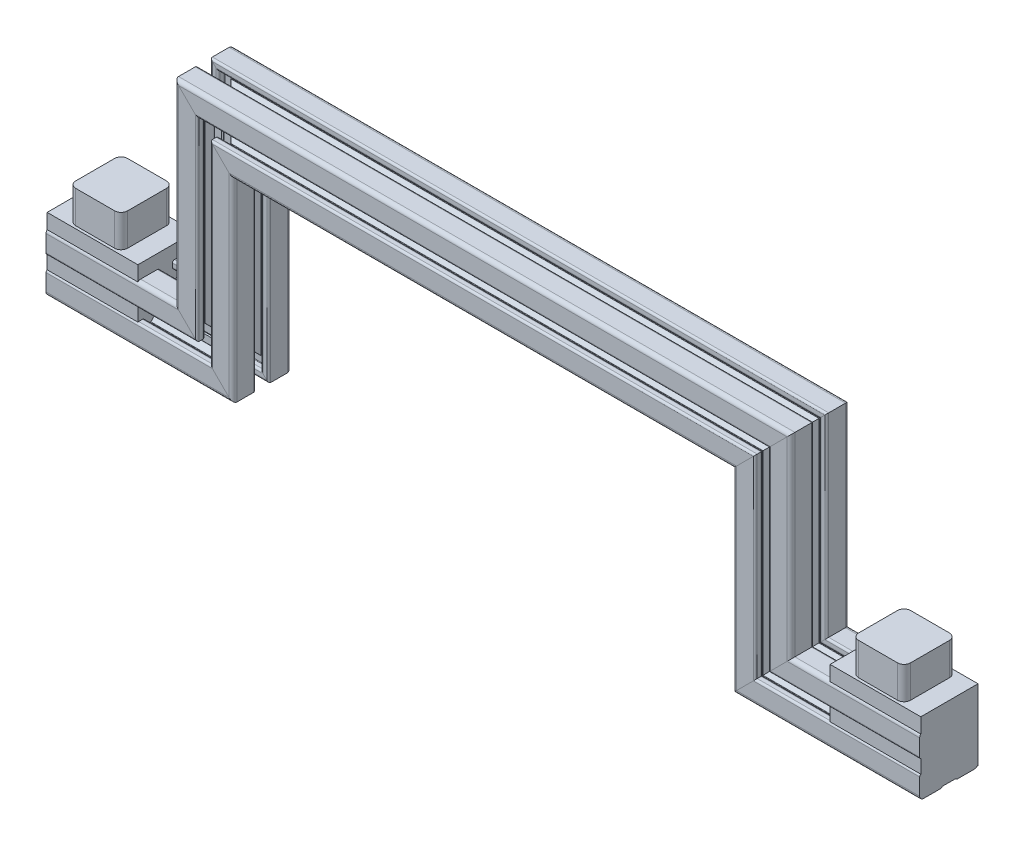
SolidWorks part; units mm, degrees
material "Commercially Pure CP-Ti UNS R50400 (SS)"
ref_plane "Front Plane" through (0, 0, 0) normal (0, 0, 1) x (1, 0, 0)
ref_plane "Top Plane" through (0, 0, 0) normal (0, 1, 0) x (1, 0, 0)
ref_plane "Right Plane" through (0, 0, 0) normal (1, 0, 0) x (0, 0, -1)
sketch "Sketch7" plane through (0, 0, 0) normal (1, 0, 0) x (0, 0, -1)
  line L0 (13.9698, 21.2743) -> (13.5298, 21.2743)
  line L1 (12.0298, 22.7743) -> (12.0298, 23.2743)
  line L2 (13.5298, 24.7743) -> (23.1398, 24.7743)
  line L3 (25.4198, 22.4943) -> (25.4198, 12.8843)
  line L4 (23.9198, 11.3843) -> (23.4198, 11.3843)
  line L5 (21.9198, 12.8843) -> (21.9198, 13.3243)
  line L6 (20.9198, 14.3243) -> (15.3498, 14.3243)
  line L7 (14.9698, 14.7043) -> (14.9698, 20.2743)
  line L8 (21.9589, -6.6897) -> (21.9589, -6.2497)
  line L9 (23.4589, -4.7497) -> (23.9589, -4.7497)
  line L10 (25.4589, -6.2497) -> (25.4589, -15.8597)
  line L11 (23.1789, -18.1397) -> (13.5689, -18.1397)
  line L12 (12.0689, -16.6397) -> (12.0689, -16.1397)
  line L13 (13.5689, -14.6397) -> (14.0089, -14.6397)
  line L14 (15.0089, -13.6397) -> (15.0089, -8.0697)
  line L15 (15.3889, -7.6897) -> (20.9589, -7.6897)
  line L16 (-6.0052, -14.6787) -> (-5.5652, -14.6787)
  line L17 (-4.0652, -16.1787) -> (-4.0652, -16.6787)
  line L18 (-5.5652, -18.1787) -> (-15.1752, -18.1787)
  line L19 (-17.4552, -15.8987) -> (-17.4552, -6.2887)
  line L20 (-15.9552, -4.7887) -> (-15.4552, -4.7887)
  line L21 (-13.9552, -6.2887) -> (-13.9552, -6.7287)
  line L22 (-12.9552, -7.7287) -> (-7.3852, -7.7287)
  line L23 (-7.0052, -8.1087) -> (-7.0052, -13.6787)
  line L24 (1.8289, -2.4886) -> (1.4132, -2.3164)
  line L25 (-1.632, 0.7289) -> (-1.8042, 1.1447)
  line L26 (-1.804, 5.4512) -> (-1.6318, 5.867)
  line L27 (1.4134, 8.9121) -> (1.8292, 9.0843)
  line L28 (6.1358, 9.0842) -> (6.5515, 8.912)
  line L29 (9.5966, 5.8667) -> (9.7688, 5.451)
  line L30 (9.7687, 1.1444) -> (9.5965, 0.7287)
  line L31 (6.5512, -2.3165) -> (6.1355, -2.4887)
  line L32 (-13.9942, 13.2853) -> (-13.9942, 12.8453)
  line L33 (-15.4942, 11.3453) -> (-15.9942, 11.3453)
  line L34 (-17.4942, 12.8453) -> (-17.4942, 22.4553)
  line L35 (-15.2142, 24.7353) -> (-5.6042, 24.7353)
  line L36 (-4.1042, 23.2353) -> (-4.1042, 22.7353)
  line L37 (-5.6042, 21.2353) -> (-6.0442, 21.2353)
  line L38 (-7.0442, 20.2353) -> (-7.0442, 14.6653)
  line L39 (-7.4242, 14.2853) -> (-12.9942, 14.2853)
  line L40 (4.9058, 11.2153) -> (4.0058, 10.7002)
  line L41 (4.0058, 10.7002) -> (3.1058, 11.2153)
  line L42 (3.1058, 11.2153) -> (-2.1975, 11.2153)
  line L43 (-2.4662, 11.3266) -> (-5.9329, 14.7933)
  line L44 (-6.0442, 15.062) -> (-6.0442, 19.3553)
  line L45 (-5.6642, 19.7353) -> (-2.5792, 19.7353)
  line L46 (-1.0592, 21.2553) -> (-1.0592, 24.2153)
  line L47 (-2.5792, 25.7353) -> (-15.4942, 25.7353)
  line L48 (-18.4942, 22.7353) -> (-18.4942, 9.8203)
  line L49 (-16.9742, 8.3003) -> (-14.0142, 8.3003)
  line L50 (-12.4942, 9.8203) -> (-12.4942, 12.9053)
  line L51 (-12.1142, 13.2853) -> (-7.8138, 13.2853)
  line L52 (-7.5451, 13.174) -> (-4.0855, 9.7144)
  line L53 (-3.9742, 9.4457) -> (-3.9742, 4.1353)
  line L54 (-3.9742, 4.1353) -> (-3.4546, 3.2353)
  line L55 (-3.4546, 3.2353) -> (-3.9742, 2.3353)
  line L56 (-3.9742, 2.3353) -> (-3.9742, -2.968)
  line L57 (-4.0855, -3.2367) -> (-7.5522, -6.7034)
  line L58 (-7.8209, -6.8147) -> (-12.1142, -6.8147)
  line L59 (-12.4942, -6.4347) -> (-12.4942, -3.3497)
  line L60 (-14.0142, -1.8297) -> (-16.9742, -1.8297)
  line L61 (-18.4942, -3.3497) -> (-18.4942, -16.2647)
  line L62 (-15.4942, -19.2647) -> (-2.5792, -19.2647)
  line L63 (-1.0592, -17.7447) -> (-1.0592, -14.7847)
  line L64 (-2.5792, -13.2647) -> (-5.6642, -13.2647)
  line L65 (-6.0442, -12.8847) -> (-6.0442, -8.5843)
  line L66 (-5.9329, -8.3156) -> (-2.4733, -4.856)
  line L67 (-2.2046, -4.7447) -> (3.1058, -4.7447)
  line L68 (3.1058, -4.7447) -> (4.0058, -4.2295)
  line L69 (4.0058, -4.2295) -> (4.9058, -4.7447)
  line L70 (4.9058, -4.7447) -> (10.2091, -4.7447)
  line L71 (10.4778, -4.856) -> (13.9445, -8.3227)
  line L72 (14.0558, -8.5914) -> (14.0558, -12.8847)
  line L73 (13.6758, -13.2647) -> (10.5908, -13.2647)
  line L74 (9.0708, -14.7847) -> (9.0708, -17.7447)
  line L75 (10.5908, -19.2647) -> (23.5058, -19.2647)
  line L76 (26.5058, -16.2647) -> (26.5058, -3.3497)
  line L77 (24.9858, -1.8297) -> (22.0258, -1.8297)
  line L78 (20.5058, -3.3497) -> (20.5058, -6.4347)
  line L79 (20.1258, -6.8147) -> (15.8254, -6.8147)
  line L80 (15.5567, -6.7034) -> (12.0971, -3.2438)
  line L81 (11.9858, -2.9751) -> (11.9858, 2.3353)
  line L82 (11.9858, 2.3353) -> (11.4662, 3.2353)
  line L83 (11.4662, 3.2353) -> (11.9858, 4.1353)
  line L84 (11.9858, 4.1353) -> (11.9858, 9.4386)
  line L85 (12.0971, 9.7073) -> (15.5638, 13.174)
  line L86 (15.8325, 13.2853) -> (20.1258, 13.2853)
  line L87 (20.5058, 12.9053) -> (20.5058, 9.8203)
  line L88 (22.0258, 8.3003) -> (24.9858, 8.3003)
  line L89 (26.5058, 9.8203) -> (26.5058, 22.7353)
  line L90 (23.5058, 25.7353) -> (10.5908, 25.7353)
  line L91 (9.0708, 24.2153) -> (9.0708, 21.2553)
  line L92 (10.5908, 19.7353) -> (13.6758, 19.7353)
  line L93 (14.0558, 19.3553) -> (14.0558, 15.0549)
  line L94 (13.9445, 14.7862) -> (10.4849, 11.3266)
  line L95 (10.2162, 11.2153) -> (4.9058, 11.2153)
  arc A0 (14.9698, 20.2743) -> (13.9698, 21.2743) centre (13.9698, 20.2743) ccw
  arc A1 (12.0298, 22.7743) -> (13.5298, 21.2743) centre (13.5298, 22.7743) ccw
  arc A2 (13.5298, 24.7743) -> (12.0298, 23.2743) centre (13.5298, 23.2743) ccw
  arc A3 (25.4198, 22.4943) -> (23.1398, 24.7743) centre (23.1398, 22.4943) ccw
  arc A4 (23.9198, 11.3843) -> (25.4198, 12.8843) centre (23.9198, 12.8843) ccw
  arc A5 (21.9198, 12.8843) -> (23.4198, 11.3843) centre (23.4198, 12.8843) ccw
  arc A6 (21.9198, 13.3243) -> (20.9198, 14.3243) centre (20.9198, 13.3243) ccw
  arc A7 (14.9698, 14.7043) -> (15.3498, 14.3243) centre (15.3498, 14.7043) ccw
  arc A8 (20.9589, -7.6897) -> (21.9589, -6.6897) centre (20.9589, -6.6897) ccw
  arc A9 (23.4589, -4.7497) -> (21.9589, -6.2497) centre (23.4589, -6.2497) ccw
  arc A10 (25.4589, -6.2497) -> (23.9589, -4.7497) centre (23.9589, -6.2497) ccw
  arc A11 (23.1789, -18.1397) -> (25.4589, -15.8597) centre (23.1789, -15.8597) ccw
  arc A12 (12.0689, -16.6397) -> (13.5689, -18.1397) centre (13.5689, -16.6397) ccw
  arc A13 (13.5689, -14.6397) -> (12.0689, -16.1397) centre (13.5689, -16.1397) ccw
  arc A14 (14.0089, -14.6397) -> (15.0089, -13.6397) centre (14.0089, -13.6397) ccw
  arc A15 (15.3889, -7.6897) -> (15.0089, -8.0697) centre (15.3889, -8.0697) ccw
  arc A16 (-7.0052, -13.6787) -> (-6.0052, -14.6787) centre (-6.0052, -13.6787) ccw
  arc A17 (-4.0652, -16.1787) -> (-5.5652, -14.6787) centre (-5.5652, -16.1787) ccw
  arc A18 (-5.5652, -18.1787) -> (-4.0652, -16.6787) centre (-5.5652, -16.6787) ccw
  arc A19 (-17.4552, -15.8987) -> (-15.1752, -18.1787) centre (-15.1752, -15.8987) ccw
  arc A20 (-15.9552, -4.7887) -> (-17.4552, -6.2887) centre (-15.9552, -6.2887) ccw
  arc A21 (-13.9552, -6.2887) -> (-15.4552, -4.7887) centre (-15.4552, -6.2887) ccw
  arc A22 (-13.9552, -6.7287) -> (-12.9552, -7.7287) centre (-12.9552, -6.7287) ccw
  arc A23 (-7.0052, -8.1087) -> (-7.3852, -7.7287) centre (-7.3852, -8.1087) ccw
  arc A24 (1.0363, -0.7421) -> (1.4132, -2.3164) centre (1.7959, -1.3925) ccw
  arc A25 (-0.0577, 0.352) -> (1.0363, -0.7421) centre (3.9823, 3.2978) ccw
  arc A26 (-1.632, 0.7289) -> (-0.0577, 0.352) centre (-0.7081, 1.1116) ccw
  arc A27 (-0.9575, 2.5244) -> (-1.8042, 1.1447) centre (-0.8803, 1.5274) ccw
  arc A28 (-0.9574, 4.0715) -> (-0.9575, 2.5244) centre (3.9823, 3.2978) ccw
  arc A29 (-1.804, 5.4512) -> (-0.9574, 4.0715) centre (-0.8802, 5.0686) ccw
  arc A30 (-0.0575, 6.2439) -> (-1.6318, 5.867) centre (-0.708, 5.4843) ccw
  arc A31 (1.0365, 7.3379) -> (-0.0575, 6.2439) centre (3.9823, 3.2978) ccw
  arc A32 (1.4134, 8.9121) -> (1.0365, 7.3379) centre (1.7961, 7.9882) ccw
  arc A33 (3.2089, 8.2376) -> (1.8292, 9.0843) centre (2.2119, 8.1604) ccw
  arc A34 (4.7561, 8.2376) -> (3.2089, 8.2376) centre (3.9823, 3.2978) ccw
  arc A35 (6.1358, 9.0842) -> (4.7561, 8.2376) centre (5.7531, 8.1603) ccw
  arc A36 (6.9284, 7.3377) -> (6.5515, 8.912) centre (6.1688, 7.9881) ccw
  arc A37 (8.0224, 6.2437) -> (6.9284, 7.3377) centre (3.9823, 3.2978) ccw
  arc A38 (9.5966, 5.8667) -> (8.0224, 6.2437) centre (8.6727, 5.484) ccw
  arc A39 (8.9222, 4.0713) -> (9.7688, 5.451) centre (8.845, 5.0683) ccw
  arc A40 (8.9221, 2.5241) -> (8.9222, 4.0713) centre (3.9823, 3.2978) ccw
  arc A41 (9.7687, 1.1444) -> (8.9221, 2.5241) centre (8.8448, 1.5271) ccw
  arc A42 (8.0222, 0.3518) -> (9.5965, 0.7287) centre (8.6726, 1.1113) ccw
  arc A43 (6.9282, -0.7422) -> (8.0222, 0.3518) centre (3.9823, 3.2978) ccw
  arc A44 (6.5512, -2.3165) -> (6.9282, -0.7422) centre (6.1685, -1.3926) ccw
  arc A45 (4.7558, -1.642) -> (6.1355, -2.4887) centre (5.7528, -1.5648) ccw
  arc A46 (3.2086, -1.642) -> (4.7558, -1.642) centre (3.9823, 3.2978) ccw
  arc A47 (1.8289, -2.4886) -> (3.2086, -1.642) centre (2.2116, -1.5647) ccw
  arc A48 (-12.9942, 14.2853) -> (-13.9942, 13.2853) centre (-12.9942, 13.2853) ccw
  arc A49 (-15.4942, 11.3453) -> (-13.9942, 12.8453) centre (-15.4942, 12.8453) ccw
  arc A50 (-17.4942, 12.8453) -> (-15.9942, 11.3453) centre (-15.9942, 12.8453) ccw
  arc A51 (-15.2142, 24.7353) -> (-17.4942, 22.4553) centre (-15.2142, 22.4553) ccw
  arc A52 (-4.1042, 23.2353) -> (-5.6042, 24.7353) centre (-5.6042, 23.2353) ccw
  arc A53 (-5.6042, 21.2353) -> (-4.1042, 22.7353) centre (-5.6042, 22.7353) ccw
  arc A54 (-6.0442, 21.2353) -> (-7.0442, 20.2353) centre (-6.0442, 20.2353) ccw
  arc A55 (-7.4242, 14.2853) -> (-7.0442, 14.6653) centre (-7.4242, 14.6653) ccw
  arc A56 (-2.4662, 11.3266) -> (-2.1975, 11.2153) centre (-2.1975, 11.5953) ccw
  arc A57 (-6.0442, 15.062) -> (-5.9329, 14.7933) centre (-5.6642, 15.062) ccw
  arc A58 (-5.6642, 19.7353) -> (-6.0442, 19.3553) centre (-5.6642, 19.3553) ccw
  arc A59 (-2.5792, 19.7353) -> (-1.0592, 21.2553) centre (-2.5792, 21.2553) ccw
  arc A60 (-1.0592, 24.2153) -> (-2.5792, 25.7353) centre (-2.5792, 24.2153) ccw
  arc A61 (-15.4942, 25.7353) -> (-18.4942, 22.7353) centre (-15.4942, 22.7353) ccw
  arc A62 (-18.4942, 9.8203) -> (-16.9742, 8.3003) centre (-16.9742, 9.8203) ccw
  arc A63 (-14.0142, 8.3003) -> (-12.4942, 9.8203) centre (-14.0142, 9.8203) ccw
  arc A64 (-12.1142, 13.2853) -> (-12.4942, 12.9053) centre (-12.1142, 12.9053) ccw
  arc A65 (-7.5451, 13.174) -> (-7.8138, 13.2853) centre (-7.8138, 12.9053) ccw
  arc A66 (-3.9742, 9.4457) -> (-4.0855, 9.7144) centre (-4.3542, 9.4457) ccw
  arc A67 (-4.0855, -3.2367) -> (-3.9742, -2.968) centre (-4.3542, -2.968) ccw
  arc A68 (-7.8209, -6.8147) -> (-7.5522, -6.7034) centre (-7.8209, -6.4347) ccw
  arc A69 (-12.4942, -6.4347) -> (-12.1142, -6.8147) centre (-12.1142, -6.4347) ccw
  arc A70 (-12.4942, -3.3497) -> (-14.0142, -1.8297) centre (-14.0142, -3.3497) ccw
  arc A71 (-16.9742, -1.8297) -> (-18.4942, -3.3497) centre (-16.9742, -3.3497) ccw
  arc A72 (-18.4942, -16.2647) -> (-15.4942, -19.2647) centre (-15.4942, -16.2647) ccw
  arc A73 (-2.5792, -19.2647) -> (-1.0592, -17.7447) centre (-2.5792, -17.7447) ccw
  arc A74 (-1.0592, -14.7847) -> (-2.5792, -13.2647) centre (-2.5792, -14.7847) ccw
  arc A75 (-6.0442, -12.8847) -> (-5.6642, -13.2647) centre (-5.6642, -12.8847) ccw
  arc A76 (-5.9329, -8.3156) -> (-6.0442, -8.5843) centre (-5.6642, -8.5843) ccw
  arc A77 (-2.2046, -4.7447) -> (-2.4733, -4.856) centre (-2.2046, -5.1247) ccw
  arc A78 (10.4778, -4.856) -> (10.2091, -4.7447) centre (10.2091, -5.1247) ccw
  arc A79 (14.0558, -8.5914) -> (13.9445, -8.3227) centre (13.6758, -8.5914) ccw
  arc A80 (13.6758, -13.2647) -> (14.0558, -12.8847) centre (13.6758, -12.8847) ccw
  arc A81 (10.5908, -13.2647) -> (9.0708, -14.7847) centre (10.5908, -14.7847) ccw
  arc A82 (9.0708, -17.7447) -> (10.5908, -19.2647) centre (10.5908, -17.7447) ccw
  arc A83 (23.5058, -19.2647) -> (26.5058, -16.2647) centre (23.5058, -16.2647) ccw
  arc A84 (26.5058, -3.3497) -> (24.9858, -1.8297) centre (24.9858, -3.3497) ccw
  arc A85 (22.0258, -1.8297) -> (20.5058, -3.3497) centre (22.0258, -3.3497) ccw
  arc A86 (20.1258, -6.8147) -> (20.5058, -6.4347) centre (20.1258, -6.4347) ccw
  arc A87 (15.5567, -6.7034) -> (15.8254, -6.8147) centre (15.8254, -6.4347) ccw
  arc A88 (11.9858, -2.9751) -> (12.0971, -3.2438) centre (12.3658, -2.9751) ccw
  arc A89 (12.0971, 9.7073) -> (11.9858, 9.4386) centre (12.3658, 9.4386) ccw
  arc A90 (15.8325, 13.2853) -> (15.5638, 13.174) centre (15.8325, 12.9053) ccw
  arc A91 (20.5058, 12.9053) -> (20.1258, 13.2853) centre (20.1258, 12.9053) ccw
  arc A92 (20.5058, 9.8203) -> (22.0258, 8.3003) centre (22.0258, 9.8203) ccw
  arc A93 (24.9858, 8.3003) -> (26.5058, 9.8203) centre (24.9858, 9.8203) ccw
  arc A94 (26.5058, 22.7353) -> (23.5058, 25.7353) centre (23.5058, 22.7353) ccw
  arc A95 (10.5908, 25.7353) -> (9.0708, 24.2153) centre (10.5908, 24.2153) ccw
  arc A96 (9.0708, 21.2553) -> (10.5908, 19.7353) centre (10.5908, 21.2553) ccw
  arc A97 (14.0558, 19.3553) -> (13.6758, 19.7353) centre (13.6758, 19.3553) ccw
  arc A98 (13.9445, 14.7862) -> (14.0558, 15.0549) centre (13.6758, 15.0549) ccw
  arc A99 (10.2162, 11.2153) -> (10.4849, 11.3266) centre (10.2162, 11.5953) ccw
sketch "Sketch1" plane through (0, 0, 0) normal (0, 0, 1) x (1, 0, 0)
  line L0 (0, 0) -> (125, 0)
  line L1 (125, 0) -> (125, 150)
  line L2 (125, 150) -> (337, 150)
  dimension "D1" = 337
  dimension "D2" = 125
  dimension "D3" = 150
sketch "Sketch2" [suppressed] plane through (0, 0, 0) normal (1, 0, 0) x (0, 0, -1)
  line L0 (-33.5, -41) -> (-31.5, -41)
  line L1 (-31.5, -43) -> (-42, -43)
  line L2 (-43, -42) -> (-43, -31.5)
  line L3 (-41, -31.5) -> (-41, -33.5)
  line L4 (-40, -34.5) -> (-34.88, -34.5)
  line L5 (-34.5, -34.88) -> (-34.5, -40)
  line L6 (-16.657, -26.2238) -> (-18.284, -25.188)
  line L7 (-19.8123, -26.7162) -> (-18.7764, -28.3429)
  line L8 (-21.0015, -29.2647) -> (-21.4195, -27.3819)
  line L9 (-23.5808, -27.3818) -> (-23.9986, -29.2645)
  line L10 (-26.2238, -28.343) -> (-25.188, -26.716)
  line L11 (-26.7162, -25.1877) -> (-28.3429, -26.2236)
  line L12 (-29.2647, -23.9985) -> (-27.3819, -23.5805)
  line L13 (-27.3818, -21.4192) -> (-29.2645, -21.0014)
  line L14 (-28.343, -18.7762) -> (-26.716, -19.812)
  line L15 (-25.1877, -18.2838) -> (-26.2236, -16.6571)
  line L16 (-23.9985, -15.7353) -> (-23.5805, -17.6181)
  line L17 (-21.4192, -17.6182) -> (-21.0014, -15.7355)
  line L18 (-18.7762, -16.657) -> (-19.812, -18.284)
  line L19 (-18.2838, -19.8123) -> (-16.6571, -18.7764)
  line L20 (-15.7353, -21.0015) -> (-17.6181, -21.4195)
  line L21 (-17.6182, -23.5808) -> (-15.7355, -23.9986)
  line L22 (41, -33.5) -> (41, -31.5)
  line L23 (43, -31.5) -> (43, -42)
  line L24 (42, -43) -> (31.5, -43)
  line L25 (31.5, -41) -> (33.5, -41)
  line L26 (34.5, -40) -> (34.5, -34.88)
  line L27 (34.88, -34.5) -> (40, -34.5)
  line L28 (26.7162, -19.8123) -> (28.3429, -18.7764)
  line L29 (29.2647, -21.0015) -> (27.3819, -21.4195)
  line L30 (27.3818, -23.5808) -> (29.2645, -23.9986)
  line L31 (28.343, -26.2238) -> (26.716, -25.188)
  line L32 (25.1877, -26.7162) -> (26.2236, -28.3429)
  line L33 (23.9985, -29.2647) -> (23.5805, -27.3819)
  line L34 (21.4192, -27.3818) -> (21.0014, -29.2645)
  line L35 (18.7762, -28.343) -> (19.812, -26.716)
  line L36 (18.2838, -25.1877) -> (16.6571, -26.2236)
  line L37 (15.7353, -23.9985) -> (17.6181, -23.5805)
  line L38 (17.6182, -21.4192) -> (15.7355, -21.0014)
  line L39 (16.657, -18.7762) -> (18.284, -19.812)
  line L40 (19.8123, -18.2838) -> (18.7764, -16.6571)
  line L41 (21.0015, -15.7353) -> (21.4195, -17.6181)
  line L42 (23.5808, -17.6182) -> (23.9986, -15.7355)
  line L43 (26.2238, -16.657) -> (25.188, -18.284)
  line L44 (34.5, 34.88) -> (34.5, 40)
  line L45 (33.5, 41) -> (31.5, 41)
  line L46 (31.5, 43) -> (42, 43)
  line L47 (43, 42) -> (43, 31.5)
  line L48 (41, 31.5) -> (41, 33.5)
  line L49 (40, 34.5) -> (34.88, 34.5)
  line L50 (26.7162, 25.1877) -> (28.3429, 26.2236)
  line L51 (29.2647, 23.9985) -> (27.3819, 23.5805)
  line L52 (27.3818, 21.4192) -> (29.2645, 21.0014)
  line L53 (28.343, 18.7762) -> (26.716, 19.812)
  line L54 (25.1877, 18.2838) -> (26.2236, 16.6571)
  line L55 (23.9985, 15.7353) -> (23.5805, 17.6181)
  line L56 (21.4192, 17.6182) -> (21.0014, 15.7355)
  line L57 (18.7762, 16.657) -> (19.812, 18.284)
  line L58 (18.2838, 19.8123) -> (16.6571, 18.7764)
  line L59 (15.7353, 21.0015) -> (17.6181, 21.4195)
  line L60 (17.6182, 23.5808) -> (15.7355, 23.9986)
  line L61 (16.657, 26.2238) -> (18.284, 25.188)
  line L62 (19.8123, 26.7162) -> (18.7764, 28.3429)
  line L63 (21.0015, 29.2647) -> (21.4195, 27.3819)
  line L64 (23.5808, 27.3818) -> (23.9986, 29.2645)
  line L65 (26.2238, 28.343) -> (25.188, 26.716)
  line L66 (-41, 33.5) -> (-41, 31.5)
  line L67 (-43, 31.5) -> (-43, 42)
  line L68 (-42, 43) -> (-31.5, 43)
  line L69 (-31.5, 41) -> (-33.5, 41)
  line L70 (-34.5, 40) -> (-34.5, 34.88)
  line L71 (-34.88, 34.5) -> (-40, 34.5)
  line L72 (-16.657, 18.7762) -> (-18.284, 19.812)
  line L73 (-19.8123, 18.2838) -> (-18.7764, 16.6571)
  line L74 (-21.0015, 15.7353) -> (-21.4195, 17.6181)
  line L75 (-23.5808, 17.6182) -> (-23.9986, 15.7355)
  line L76 (-26.2238, 16.657) -> (-25.188, 18.284)
  line L77 (-26.7162, 19.8123) -> (-28.3429, 18.7764)
  line L78 (-29.2647, 21.0015) -> (-27.3819, 21.4195)
  line L79 (-27.3818, 23.5808) -> (-29.2645, 23.9986)
  line L80 (-28.343, 26.2238) -> (-26.716, 25.188)
  line L81 (-25.1877, 26.7162) -> (-26.2236, 28.3429)
  line L82 (-23.9985, 29.2647) -> (-23.5805, 27.3819)
  line L83 (-21.4192, 27.3818) -> (-21.0014, 29.2645)
  line L84 (-18.7762, 28.343) -> (-19.812, 26.716)
  line L85 (-18.2838, 25.1877) -> (-16.6571, 26.2236)
  line L86 (-15.7353, 23.9985) -> (-17.6181, 23.5805)
  line L87 (-17.6182, 21.4192) -> (-15.7355, 21.0014)
  line L88 (39, -10.16) -> (33.3774, -10.16)
  line L89 (31.9632, -10.7458) -> (29.8203, -12.8887)
  line L90 (29.5516, -13) -> (23.4, -13)
  line L91 (23.4, -13) -> (22.5, -13.5151)
  line L92 (22.5, -13.5151) -> (21.6, -13)
  line L93 (21.6, -13) -> (15, -13)
  line L94 (13, -15) -> (13, -21.6)
  line L95 (13, -21.6) -> (13.5196, -22.5)
  line L96 (13.5196, -22.5) -> (13, -23.4)
  line L97 (13, -23.4) -> (13, -29.5516)
  line L98 (12.8887, -29.8203) -> (11.3787, -31.3303)
  line L99 (10.5, -33.4516) -> (10.5, -40)
  line L100 (11.5, -41) -> (13.5, -41)
  line L101 (13.5, -43) -> (-13.5, -43)
  line L102 (-13.5, -41) -> (-11.5, -41)
  line L103 (-10.5, -40) -> (-10.5, -33.4516)
  line L104 (-11.3787, -31.3303) -> (-12.8887, -29.8203)
  line L105 (-13, -29.5516) -> (-13, -23.4)
  line L106 (-13, -23.4) -> (-13.5196, -22.5)
  line L107 (-13.5196, -22.5) -> (-13, -21.6)
  line L108 (-13, -21.6) -> (-13, -15)
  line L109 (-15, -13) -> (-21.6, -13)
  line L110 (-21.6, -13) -> (-22.5, -13.5151)
  line L111 (-22.5, -13.5151) -> (-23.4, -13)
  line L112 (-23.4, -13) -> (-29.5516, -13)
  line L113 (-29.8203, -12.8887) -> (-31.9632, -10.7458)
  line L114 (-33.3774, -10.16) -> (-39, -10.16)
  line L115 (-41, -12.16) -> (-41, -13.5)
  line L116 (-43, -13.5) -> (-43, 13.5)
  line L117 (-41, 13.5) -> (-41, 12.16)
  line L118 (-39, 10.16) -> (-33.3774, 10.16)
  line L119 (-31.9632, 10.7458) -> (-29.8203, 12.8887)
  line L120 (-29.5516, 13) -> (-23.4, 13)
  line L121 (-23.4, 13) -> (-22.5, 13.5151)
  line L122 (-22.5, 13.5151) -> (-21.6, 13)
  line L123 (-21.6, 13) -> (-15, 13)
  line L124 (-13, 15) -> (-13, 21.6)
  line L125 (-13, 21.6) -> (-13.5196, 22.5)
  line L126 (-13.5196, 22.5) -> (-13, 23.4)
  line L127 (-13, 23.4) -> (-13, 29.5516)
  line L128 (-12.8887, 29.8203) -> (-11.3787, 31.3303)
  line L129 (-10.5, 33.4516) -> (-10.5, 40)
  line L130 (-11.5, 41) -> (-13.5, 41)
  line L131 (-13.5, 43) -> (13.5, 43)
  line L132 (13.5, 41) -> (11.5, 41)
  line L133 (10.5, 40) -> (10.5, 33.4516)
  line L134 (11.3787, 31.3303) -> (12.8887, 29.8203)
  line L135 (13, 29.5516) -> (13, 23.4)
  line L136 (13, 23.4) -> (13.5196, 22.5)
  line L137 (13.5196, 22.5) -> (13, 21.6)
  line L138 (13, 21.6) -> (13, 15)
  line L139 (15, 13) -> (21.6, 13)
  line L140 (21.6, 13) -> (22.5, 13.5151)
  line L141 (22.5, 13.5151) -> (23.4, 13)
  line L142 (23.4, 13) -> (29.5516, 13)
  line L143 (29.8203, 12.8887) -> (31.9581, 10.7509)
  line L144 (33.3723, 10.1651) -> (39, 10.1651)
  line L145 (41, 12.1651) -> (41, 13.5)
  line L146 (43, 13.5) -> (43, -13.5)
  line L147 (41, -13.5) -> (41, -12.16)
  line L148 (45, -15.915) -> (45, 15.915)
  line L149 (43.48, 17.435) -> (40.52, 17.435)
  line L150 (39, 15.915) -> (39, 13.45)
  line L151 (38, 12.45) -> (34.9984, 12.45)
  line L152 (34.7297, 12.5613) -> (32.1113, 15.1797)
  line L153 (32, 15.4484) -> (32, 21.6)
  line L154 (32, 21.6) -> (31.4804, 22.5)
  line L155 (31.4804, 22.5) -> (32, 23.4)
  line L156 (32, 23.4) -> (32, 29.5516)
  line L157 (32.1113, 29.8203) -> (34.7297, 32.4387)
  line L158 (34.9984, 32.55) -> (38, 32.55)
  line L159 (39, 31.55) -> (39, 29.085)
  line L160 (40.52, 27.565) -> (43.48, 27.565)
  line L161 (45, 29.085) -> (45, 42)
  line L162 (42, 45) -> (29.085, 45)
  line L163 (27.565, 43.48) -> (27.565, 40.52)
  line L164 (29.085, 39) -> (31.55, 39)
  line L165 (32.55, 38) -> (32.55, 34.9984)
  line L166 (32.4387, 34.7297) -> (29.8203, 32.1113)
  line L167 (29.5516, 32) -> (23.4, 32)
  line L168 (23.4, 32) -> (22.5, 31.4849)
  line L169 (22.5, 31.4849) -> (21.6, 32)
  line L170 (21.6, 32) -> (15.4484, 32)
  line L171 (15.1797, 32.1113) -> (12.5613, 34.7297)
  line L172 (12.45, 34.9984) -> (12.45, 38)
  line L173 (13.45, 39) -> (15.915, 39)
  line L174 (17.435, 40.52) -> (17.435, 43.48)
  line L175 (15.915, 45) -> (-15.915, 45)
  line L176 (-17.435, 43.48) -> (-17.435, 40.52)
  line L177 (-15.915, 39) -> (-13.45, 39)
  line L178 (-12.45, 38) -> (-12.45, 34.9984)
  line L179 (-12.5613, 34.7297) -> (-15.1797, 32.1113)
  line L180 (-15.4484, 32) -> (-21.6, 32)
  line L181 (-21.6, 32) -> (-22.5, 31.4849)
  line L182 (-22.5, 31.4849) -> (-23.4, 32)
  line L183 (-23.4, 32) -> (-29.5516, 32)
  line L184 (-29.8203, 32.1113) -> (-32.4387, 34.7297)
  line L185 (-32.55, 34.9984) -> (-32.55, 38)
  line L186 (-31.55, 39) -> (-29.085, 39)
  line L187 (-27.565, 40.52) -> (-27.565, 43.48)
  line L188 (-29.085, 45) -> (-42, 45)
  line L189 (-45, 42) -> (-45, 29.085)
  line L190 (-43.48, 27.565) -> (-40.52, 27.565)
  line L191 (-39, 29.085) -> (-39, 31.55)
  line L192 (-38, 32.55) -> (-34.9984, 32.55)
  line L193 (-34.7297, 32.4387) -> (-32.1113, 29.8203)
  line L194 (-32, 29.5516) -> (-32, 23.4)
  line L195 (-32, 23.4) -> (-31.4804, 22.5)
  line L196 (-31.4804, 22.5) -> (-32, 21.6)
  line L197 (-32, 21.6) -> (-32, 15.4484)
  line L198 (-32.1113, 15.1797) -> (-34.7297, 12.5613)
  line L199 (-34.9984, 12.45) -> (-38, 12.45)
  line L200 (-39, 13.45) -> (-39, 15.915)
  line L201 (-40.52, 17.435) -> (-43.48, 17.435)
  line L202 (-45, 15.915) -> (-45, -15.915)
  line L203 (-43.48, -17.435) -> (-40.52, -17.435)
  line L204 (-39, -15.915) -> (-39, -13.45)
  line L205 (-38, -12.45) -> (-34.9984, -12.45)
  line L206 (-34.7297, -12.5613) -> (-32.1113, -15.1797)
  line L207 (-32, -15.4484) -> (-32, -21.6)
  line L208 (-32, -21.6) -> (-31.4804, -22.5)
  line L209 (-31.4804, -22.5) -> (-32, -23.4)
  line L210 (-32, -23.4) -> (-32, -29.5516)
  line L211 (-32.1113, -29.8203) -> (-34.7297, -32.4387)
  line L212 (-34.9984, -32.55) -> (-38, -32.55)
  line L213 (-39, -31.55) -> (-39, -29.085)
  line L214 (-40.52, -27.565) -> (-43.48, -27.565)
  line L215 (-45, -29.085) -> (-45, -42)
  line L216 (-42, -45) -> (-29.085, -45)
  line L217 (-27.565, -43.48) -> (-27.565, -40.52)
  line L218 (-29.085, -39) -> (-31.55, -39)
  line L219 (-32.55, -38) -> (-32.55, -34.9984)
  line L220 (-32.4387, -34.7297) -> (-29.8203, -32.1113)
  line L221 (-29.5516, -32) -> (-23.4, -32)
  line L222 (-23.4, -32) -> (-22.5, -31.4849)
  line L223 (-22.5, -31.4849) -> (-21.6, -32)
  line L224 (-21.6, -32) -> (-15.4484, -32)
  line L225 (-15.1797, -32.1113) -> (-12.5613, -34.7297)
  line L226 (-12.45, -34.9984) -> (-12.45, -38)
  line L227 (-13.45, -39) -> (-15.915, -39)
  line L228 (-17.435, -40.52) -> (-17.435, -43.48)
  line L229 (-15.915, -45) -> (15.915, -45)
  line L230 (17.435, -43.48) -> (17.435, -40.52)
  line L231 (15.915, -39) -> (13.45, -39)
  line L232 (12.45, -38) -> (12.45, -34.9984)
  line L233 (12.5613, -34.7297) -> (15.1797, -32.1113)
  line L234 (15.4484, -32) -> (21.6, -32)
  line L235 (21.6, -32) -> (22.5, -31.4849)
  line L236 (22.5, -31.4849) -> (23.4, -32)
  line L237 (23.4, -32) -> (29.5516, -32)
  line L238 (29.8203, -32.1113) -> (32.4387, -34.7297)
  line L239 (32.55, -34.9984) -> (32.55, -38)
  line L240 (31.55, -39) -> (29.085, -39)
  line L241 (27.565, -40.52) -> (27.565, -43.48)
  line L242 (29.085, -45) -> (42, -45)
  line L243 (45, -42) -> (45, -29.085)
  line L244 (43.48, -27.565) -> (40.52, -27.565)
  line L245 (39, -29.085) -> (39, -31.55)
  line L246 (38, -32.55) -> (34.9984, -32.55)
  line L247 (34.7297, -32.4387) -> (32.1113, -29.8203)
  line L248 (32, -29.5516) -> (32, -23.4)
  line L249 (32, -23.4) -> (31.4804, -22.5)
  line L250 (31.4804, -22.5) -> (32, -21.6)
  line L251 (32, -21.6) -> (32, -15.4484)
  line L252 (32.1113, -15.1797) -> (34.7297, -12.5613)
  line L253 (34.9984, -12.45) -> (38, -12.45)
  line L254 (39, -13.45) -> (39, -15.915)
  line L255 (40.52, -17.435) -> (43.48, -17.435)
  arc A0 (-34.5, -40) -> (-33.5, -41) centre (-33.5, -40) ccw
  arc A1 (-31.5, -43) -> (-31.5, -41) centre (-31.5, -42) ccw
  arc A2 (-43, -42) -> (-42, -43) centre (-42, -42) ccw
  arc A3 (-41, -31.5) -> (-43, -31.5) centre (-42, -31.5) ccw
  arc A4 (-41, -33.5) -> (-40, -34.5) centre (-40, -33.5) ccw
  arc A5 (-34.5, -34.88) -> (-34.88, -34.5) centre (-34.88, -34.88) ccw
  arc A6 (-15.2086, -25.7917) -> (-15.0167, -25.3284) centre (-22.5, -22.5) ccw
  arc A7 (-16.657, -26.2238) -> (-15.2086, -25.7917) centre (-16.12, -25.3802) ccw
  arc A8 (-19.8123, -26.7162) -> (-18.284, -25.188) centre (-22.5, -22.5) ccw
  arc A9 (-19.2085, -29.7915) -> (-18.7764, -28.3429) centre (-19.6199, -28.8801) ccw
  arc A10 (-19.6717, -29.9834) -> (-19.2085, -29.7915) centre (-22.5, -22.5) ccw
  arc A11 (-21.0015, -29.2647) -> (-19.6717, -29.9834) centre (-20.0253, -29.048) ccw
  arc A12 (-23.5808, -27.3818) -> (-21.4195, -27.3819) centre (-22.5, -22.5) ccw
  arc A13 (-25.3284, -29.9833) -> (-23.9986, -29.2645) centre (-24.9749, -29.0479) ccw
  arc A14 (-25.7917, -29.7914) -> (-25.3284, -29.9833) centre (-22.5, -22.5) ccw
  arc A15 (-26.2238, -28.343) -> (-25.7917, -29.7914) centre (-25.3802, -28.88) ccw
  arc A16 (-26.7162, -25.1877) -> (-25.188, -26.716) centre (-22.5, -22.5) ccw
  arc A17 (-29.7915, -25.7915) -> (-28.3429, -26.2236) centre (-28.8801, -25.3801) ccw
  arc A18 (-29.9834, -25.3283) -> (-29.7915, -25.7915) centre (-22.5, -22.5) ccw
  arc A19 (-29.2647, -23.9985) -> (-29.9834, -25.3283) centre (-29.048, -24.9747) ccw
  arc A20 (-27.3818, -21.4192) -> (-27.3819, -23.5805) centre (-22.5, -22.5) ccw
  arc A21 (-29.9833, -19.6716) -> (-29.2645, -21.0014) centre (-29.0479, -20.0251) ccw
  arc A22 (-29.7914, -19.2083) -> (-29.9833, -19.6716) centre (-22.5, -22.5) ccw
  arc A23 (-28.343, -18.7762) -> (-29.7914, -19.2083) centre (-28.88, -19.6198) ccw
  arc A24 (-25.1877, -18.2838) -> (-26.716, -19.812) centre (-22.5, -22.5) ccw
  arc A25 (-25.7915, -15.2085) -> (-26.2236, -16.6571) centre (-25.3801, -16.1199) ccw
  arc A26 (-25.3283, -15.0166) -> (-25.7915, -15.2085) centre (-22.5, -22.5) ccw
  arc A27 (-23.9985, -15.7353) -> (-25.3283, -15.0166) centre (-24.9747, -15.952) ccw
  arc A28 (-21.4192, -17.6182) -> (-23.5805, -17.6181) centre (-22.5, -22.5) ccw
  arc A29 (-19.6716, -15.0167) -> (-21.0014, -15.7355) centre (-20.0251, -15.9521) ccw
  arc A30 (-19.2083, -15.2086) -> (-19.6716, -15.0167) centre (-22.5, -22.5) ccw
  arc A31 (-18.7762, -16.657) -> (-19.2083, -15.2086) centre (-19.6198, -16.12) ccw
  arc A32 (-18.2838, -19.8123) -> (-19.812, -18.284) centre (-22.5, -22.5) ccw
  arc A33 (-15.2085, -19.2085) -> (-16.6571, -18.7764) centre (-16.1199, -19.6199) ccw
  arc A34 (-15.0166, -19.6717) -> (-15.2085, -19.2085) centre (-22.5, -22.5) ccw
  arc A35 (-15.7353, -21.0015) -> (-15.0166, -19.6717) centre (-15.952, -20.0253) ccw
  arc A36 (-17.6182, -23.5808) -> (-17.6181, -21.4195) centre (-22.5, -22.5) ccw
  arc A37 (-15.0167, -25.3284) -> (-15.7355, -23.9986) centre (-15.9521, -24.9749) ccw
  arc A38 (40, -34.5) -> (41, -33.5) centre (40, -33.5) ccw
  arc A39 (43, -31.5) -> (41, -31.5) centre (42, -31.5) ccw
  arc A40 (42, -43) -> (43, -42) centre (42, -42) ccw
  arc A41 (31.5, -41) -> (31.5, -43) centre (31.5, -42) ccw
  arc A42 (33.5, -41) -> (34.5, -40) centre (33.5, -40) ccw
  arc A43 (34.88, -34.5) -> (34.5, -34.88) centre (34.88, -34.88) ccw
  arc A44 (26.7162, -19.8123) -> (25.188, -18.284) centre (22.5, -22.5) ccw
  arc A45 (29.7915, -19.2085) -> (28.3429, -18.7764) centre (28.8801, -19.6199) ccw
  arc A46 (29.9834, -19.6717) -> (29.7915, -19.2085) centre (22.5, -22.5) ccw
  arc A47 (29.2647, -21.0015) -> (29.9834, -19.6717) centre (29.048, -20.0253) ccw
  arc A48 (27.3818, -23.5808) -> (27.3819, -21.4195) centre (22.5, -22.5) ccw
  arc A49 (29.9833, -25.3284) -> (29.2645, -23.9986) centre (29.0479, -24.9749) ccw
  arc A50 (29.7914, -25.7917) -> (29.9833, -25.3284) centre (22.5, -22.5) ccw
  arc A51 (28.343, -26.2238) -> (29.7914, -25.7917) centre (28.88, -25.3802) ccw
  arc A52 (25.1877, -26.7162) -> (26.716, -25.188) centre (22.5, -22.5) ccw
  arc A53 (25.7915, -29.7915) -> (26.2236, -28.3429) centre (25.3801, -28.8801) ccw
  arc A54 (25.3283, -29.9834) -> (25.7915, -29.7915) centre (22.5, -22.5) ccw
  arc A55 (23.9985, -29.2647) -> (25.3283, -29.9834) centre (24.9747, -29.048) ccw
  arc A56 (21.4192, -27.3818) -> (23.5805, -27.3819) centre (22.5, -22.5) ccw
  arc A57 (19.6716, -29.9833) -> (21.0014, -29.2645) centre (20.0251, -29.0479) ccw
  arc A58 (19.2083, -29.7914) -> (19.6716, -29.9833) centre (22.5, -22.5) ccw
  arc A59 (18.7762, -28.343) -> (19.2083, -29.7914) centre (19.6198, -28.88) ccw
  arc A60 (18.2838, -25.1877) -> (19.812, -26.716) centre (22.5, -22.5) ccw
  arc A61 (15.2085, -25.7915) -> (16.6571, -26.2236) centre (16.1199, -25.3801) ccw
  arc A62 (15.0166, -25.3283) -> (15.2085, -25.7915) centre (22.5, -22.5) ccw
  arc A63 (15.7353, -23.9985) -> (15.0166, -25.3283) centre (15.952, -24.9747) ccw
  arc A64 (17.6182, -21.4192) -> (17.6181, -23.5805) centre (22.5, -22.5) ccw
  arc A65 (15.0167, -19.6716) -> (15.7355, -21.0014) centre (15.9521, -20.0251) ccw
  arc A66 (15.2086, -19.2083) -> (15.0167, -19.6716) centre (22.5, -22.5) ccw
  arc A67 (16.657, -18.7762) -> (15.2086, -19.2083) centre (16.12, -19.6198) ccw
  arc A68 (19.8123, -18.2838) -> (18.284, -19.812) centre (22.5, -22.5) ccw
  arc A69 (19.2085, -15.2085) -> (18.7764, -16.6571) centre (19.6199, -16.1199) ccw
  arc A70 (19.6717, -15.0166) -> (19.2085, -15.2085) centre (22.5, -22.5) ccw
  arc A71 (21.0015, -15.7353) -> (19.6717, -15.0166) centre (20.0253, -15.952) ccw
  arc A72 (23.5808, -17.6182) -> (21.4195, -17.6181) centre (22.5, -22.5) ccw
  arc A73 (25.3284, -15.0167) -> (23.9986, -15.7355) centre (24.9749, -15.9521) ccw
  arc A74 (25.7917, -15.2086) -> (25.3284, -15.0167) centre (22.5, -22.5) ccw
  arc A75 (26.2238, -16.657) -> (25.7917, -15.2086) centre (25.3802, -16.12) ccw
  arc A76 (34.5, 34.88) -> (34.88, 34.5) centre (34.88, 34.88) ccw
  arc A77 (34.5, 40) -> (33.5, 41) centre (33.5, 40) ccw
  arc A78 (31.5, 43) -> (31.5, 41) centre (31.5, 42) ccw
  arc A79 (43, 42) -> (42, 43) centre (42, 42) ccw
  arc A80 (41, 31.5) -> (43, 31.5) centre (42, 31.5) ccw
  arc A81 (41, 33.5) -> (40, 34.5) centre (40, 33.5) ccw
  arc A82 (26.7162, 25.1877) -> (25.188, 26.716) centre (22.5, 22.5) ccw
  arc A83 (29.7915, 25.7915) -> (28.3429, 26.2236) centre (28.8801, 25.3801) ccw
  arc A84 (29.9834, 25.3283) -> (29.7915, 25.7915) centre (22.5, 22.5) ccw
  arc A85 (29.2647, 23.9985) -> (29.9834, 25.3283) centre (29.048, 24.9747) ccw
  arc A86 (27.3818, 21.4192) -> (27.3819, 23.5805) centre (22.5, 22.5) ccw
  arc A87 (29.9833, 19.6716) -> (29.2645, 21.0014) centre (29.0479, 20.0251) ccw
  arc A88 (29.7914, 19.2083) -> (29.9833, 19.6716) centre (22.5, 22.5) ccw
  arc A89 (28.343, 18.7762) -> (29.7914, 19.2083) centre (28.88, 19.6198) ccw
  arc A90 (25.1877, 18.2838) -> (26.716, 19.812) centre (22.5, 22.5) ccw
  arc A91 (25.7915, 15.2085) -> (26.2236, 16.6571) centre (25.3801, 16.1199) ccw
  arc A92 (25.3283, 15.0166) -> (25.7915, 15.2085) centre (22.5, 22.5) ccw
  arc A93 (23.9985, 15.7353) -> (25.3283, 15.0166) centre (24.9747, 15.952) ccw
  arc A94 (21.4192, 17.6182) -> (23.5805, 17.6181) centre (22.5, 22.5) ccw
  arc A95 (19.6716, 15.0167) -> (21.0014, 15.7355) centre (20.0251, 15.9521) ccw
  arc A96 (19.2083, 15.2086) -> (19.6716, 15.0167) centre (22.5, 22.5) ccw
  arc A97 (18.7762, 16.657) -> (19.2083, 15.2086) centre (19.6198, 16.12) ccw
  arc A98 (18.2838, 19.8123) -> (19.812, 18.284) centre (22.5, 22.5) ccw
  arc A99 (15.2085, 19.2085) -> (16.6571, 18.7764) centre (16.1199, 19.6199) ccw
  arc A100 (15.0166, 19.6717) -> (15.2085, 19.2085) centre (22.5, 22.5) ccw
  arc A101 (15.7353, 21.0015) -> (15.0166, 19.6717) centre (15.952, 20.0253) ccw
  arc A102 (17.6182, 23.5808) -> (17.6181, 21.4195) centre (22.5, 22.5) ccw
  arc A103 (15.0167, 25.3284) -> (15.7355, 23.9986) centre (15.9521, 24.9749) ccw
  arc A104 (15.2086, 25.7917) -> (15.0167, 25.3284) centre (22.5, 22.5) ccw
  arc A105 (16.657, 26.2238) -> (15.2086, 25.7917) centre (16.12, 25.3802) ccw
  arc A106 (19.8123, 26.7162) -> (18.284, 25.188) centre (22.5, 22.5) ccw
  arc A107 (19.2085, 29.7915) -> (18.7764, 28.3429) centre (19.6199, 28.8801) ccw
  arc A108 (19.6717, 29.9834) -> (19.2085, 29.7915) centre (22.5, 22.5) ccw
  arc A109 (21.0015, 29.2647) -> (19.6717, 29.9834) centre (20.0253, 29.048) ccw
  arc A110 (23.5808, 27.3818) -> (21.4195, 27.3819) centre (22.5, 22.5) ccw
  arc A111 (25.3284, 29.9833) -> (23.9986, 29.2645) centre (24.9749, 29.0479) ccw
  arc A112 (25.7917, 29.7914) -> (25.3284, 29.9833) centre (22.5, 22.5) ccw
  arc A113 (26.2238, 28.343) -> (25.7917, 29.7914) centre (25.3802, 28.88) ccw
  arc A114 (-40, 34.5) -> (-41, 33.5) centre (-40, 33.5) ccw
  arc A115 (-43, 31.5) -> (-41, 31.5) centre (-42, 31.5) ccw
  arc A116 (-42, 43) -> (-43, 42) centre (-42, 42) ccw
  arc A117 (-31.5, 41) -> (-31.5, 43) centre (-31.5, 42) ccw
  arc A118 (-33.5, 41) -> (-34.5, 40) centre (-33.5, 40) ccw
  arc A119 (-34.88, 34.5) -> (-34.5, 34.88) centre (-34.88, 34.88) ccw
  arc A120 (-15.2086, 19.2083) -> (-15.0167, 19.6716) centre (-22.5, 22.5) ccw
  arc A121 (-16.657, 18.7762) -> (-15.2086, 19.2083) centre (-16.12, 19.6198) ccw
  arc A122 (-19.8123, 18.2838) -> (-18.284, 19.812) centre (-22.5, 22.5) ccw
  arc A123 (-19.2085, 15.2085) -> (-18.7764, 16.6571) centre (-19.6199, 16.1199) ccw
  arc A124 (-19.6717, 15.0166) -> (-19.2085, 15.2085) centre (-22.5, 22.5) ccw
  arc A125 (-21.0015, 15.7353) -> (-19.6717, 15.0166) centre (-20.0253, 15.952) ccw
  arc A126 (-23.5808, 17.6182) -> (-21.4195, 17.6181) centre (-22.5, 22.5) ccw
  arc A127 (-25.3284, 15.0167) -> (-23.9986, 15.7355) centre (-24.9749, 15.9521) ccw
  arc A128 (-25.7917, 15.2086) -> (-25.3284, 15.0167) centre (-22.5, 22.5) ccw
  arc A129 (-26.2238, 16.657) -> (-25.7917, 15.2086) centre (-25.3802, 16.12) ccw
  arc A130 (-26.7162, 19.8123) -> (-25.188, 18.284) centre (-22.5, 22.5) ccw
  arc A131 (-29.7915, 19.2085) -> (-28.3429, 18.7764) centre (-28.8801, 19.6199) ccw
  arc A132 (-29.9834, 19.6717) -> (-29.7915, 19.2085) centre (-22.5, 22.5) ccw
  arc A133 (-29.2647, 21.0015) -> (-29.9834, 19.6717) centre (-29.048, 20.0253) ccw
  arc A134 (-27.3818, 23.5808) -> (-27.3819, 21.4195) centre (-22.5, 22.5) ccw
  arc A135 (-29.9833, 25.3284) -> (-29.2645, 23.9986) centre (-29.0479, 24.9749) ccw
  arc A136 (-29.7914, 25.7917) -> (-29.9833, 25.3284) centre (-22.5, 22.5) ccw
  arc A137 (-28.343, 26.2238) -> (-29.7914, 25.7917) centre (-28.88, 25.3802) ccw
  arc A138 (-25.1877, 26.7162) -> (-26.716, 25.188) centre (-22.5, 22.5) ccw
  arc A139 (-25.7915, 29.7915) -> (-26.2236, 28.3429) centre (-25.3801, 28.8801) ccw
  arc A140 (-25.3283, 29.9834) -> (-25.7915, 29.7915) centre (-22.5, 22.5) ccw
  arc A141 (-23.9985, 29.2647) -> (-25.3283, 29.9834) centre (-24.9747, 29.048) ccw
  arc A142 (-21.4192, 27.3818) -> (-23.5805, 27.3819) centre (-22.5, 22.5) ccw
  arc A143 (-19.6716, 29.9833) -> (-21.0014, 29.2645) centre (-20.0251, 29.0479) ccw
  arc A144 (-19.2083, 29.7914) -> (-19.6716, 29.9833) centre (-22.5, 22.5) ccw
  arc A145 (-18.7762, 28.343) -> (-19.2083, 29.7914) centre (-19.6198, 28.88) ccw
  arc A146 (-18.2838, 25.1877) -> (-19.812, 26.716) centre (-22.5, 22.5) ccw
  arc A147 (-15.2085, 25.7915) -> (-16.6571, 26.2236) centre (-16.1199, 25.3801) ccw
  arc A148 (-15.0166, 25.3283) -> (-15.2085, 25.7915) centre (-22.5, 22.5) ccw
  arc A149 (-15.7353, 23.9985) -> (-15.0166, 25.3283) centre (-15.952, 24.9747) ccw
  arc A150 (-17.6182, 21.4192) -> (-17.6181, 23.5805) centre (-22.5, 22.5) ccw
  arc A151 (-15.0167, 19.6716) -> (-15.7355, 21.0014) centre (-15.9521, 20.0251) ccw
  arc A152 (41, -12.16) -> (39, -10.16) centre (39, -12.16) ccw
  arc A153 (33.3774, -10.16) -> (31.9632, -10.7458) centre (33.3774, -12.16) ccw
  arc A154 (29.5516, -13) -> (29.8203, -12.8887) centre (29.5516, -12.62) ccw
  arc A155 (15, -13) -> (13, -15) centre (15, -15) ccw
  arc A156 (12.8887, -29.8203) -> (13, -29.5516) centre (12.62, -29.5516) ccw
  arc A157 (11.3787, -31.3303) -> (10.5, -33.4516) centre (13.5, -33.4516) ccw
  arc A158 (10.5, -40) -> (11.5, -41) centre (11.5, -40) ccw
  arc A159 (13.5, -43) -> (13.5, -41) centre (13.5, -42) ccw
  arc A160 (-13.5, -41) -> (-13.5, -43) centre (-13.5, -42) ccw
  arc A161 (-11.5, -41) -> (-10.5, -40) centre (-11.5, -40) ccw
  arc A162 (-10.5, -33.4516) -> (-11.3787, -31.3303) centre (-13.5, -33.4516) ccw
  arc A163 (-13, -29.5516) -> (-12.8887, -29.8203) centre (-12.62, -29.5516) ccw
  arc A164 (-13, -15) -> (-15, -13) centre (-15, -15) ccw
  arc A165 (-29.8203, -12.8887) -> (-29.5516, -13) centre (-29.5516, -12.62) ccw
  arc A166 (-31.9632, -10.7458) -> (-33.3774, -10.16) centre (-33.3774, -12.16) ccw
  arc A167 (-39, -10.16) -> (-41, -12.16) centre (-39, -12.16) ccw
  arc A168 (-43, -13.5) -> (-41, -13.5) centre (-42, -13.5) ccw
  arc A169 (-41, 13.5) -> (-43, 13.5) centre (-42, 13.5) ccw
  arc A170 (-41, 12.16) -> (-39, 10.16) centre (-39, 12.16) ccw
  arc A171 (-33.3774, 10.16) -> (-31.9632, 10.7458) centre (-33.3774, 12.16) ccw
  arc A172 (-29.5516, 13) -> (-29.8203, 12.8887) centre (-29.5516, 12.62) ccw
  arc A173 (-15, 13) -> (-13, 15) centre (-15, 15) ccw
  arc A174 (-12.8887, 29.8203) -> (-13, 29.5516) centre (-12.62, 29.5516) ccw
  arc A175 (-11.3787, 31.3303) -> (-10.5, 33.4516) centre (-13.5, 33.4516) ccw
  arc A176 (-10.5, 40) -> (-11.5, 41) centre (-11.5, 40) ccw
  arc A177 (-13.5, 43) -> (-13.5, 41) centre (-13.5, 42) ccw
  arc A178 (13.5, 41) -> (13.5, 43) centre (13.5, 42) ccw
  arc A179 (11.5, 41) -> (10.5, 40) centre (11.5, 40) ccw
  arc A180 (10.5, 33.4516) -> (11.3787, 31.3303) centre (13.5, 33.4516) ccw
  arc A181 (13, 29.5516) -> (12.8887, 29.8203) centre (12.62, 29.5516) ccw
  arc A182 (13, 15) -> (15, 13) centre (15, 15) ccw
  arc A183 (29.8203, 12.8887) -> (29.5516, 13) centre (29.5516, 12.62) ccw
  arc A184 (31.9581, 10.7509) -> (33.3723, 10.1651) centre (33.3723, 12.1651) ccw
  arc A185 (39, 10.1651) -> (41, 12.1651) centre (39, 12.1651) ccw
  arc A186 (43, 13.5) -> (41, 13.5) centre (42, 13.5) ccw
  arc A187 (41, -13.5) -> (43, -13.5) centre (42, -13.5) ccw
  arc A188 (45, 15.915) -> (43.48, 17.435) centre (43.48, 15.915) ccw
  arc A189 (40.52, 17.435) -> (39, 15.915) centre (40.52, 15.915) ccw
  arc A190 (38, 12.45) -> (39, 13.45) centre (38, 13.45) ccw
  arc A191 (34.7297, 12.5613) -> (34.9984, 12.45) centre (34.9984, 12.83) ccw
  arc A192 (32, 15.4484) -> (32.1113, 15.1797) centre (32.38, 15.4484) ccw
  arc A193 (32.1113, 29.8203) -> (32, 29.5516) centre (32.38, 29.5516) ccw
  arc A194 (34.9984, 32.55) -> (34.7297, 32.4387) centre (34.9984, 32.17) ccw
  arc A195 (39, 31.55) -> (38, 32.55) centre (38, 31.55) ccw
  arc A196 (39, 29.085) -> (40.52, 27.565) centre (40.52, 29.085) ccw
  arc A197 (43.48, 27.565) -> (45, 29.085) centre (43.48, 29.085) ccw
  arc A198 (45, 42) -> (42, 45) centre (42, 42) ccw
  arc A199 (29.085, 45) -> (27.565, 43.48) centre (29.085, 43.48) ccw
  arc A200 (27.565, 40.52) -> (29.085, 39) centre (29.085, 40.52) ccw
  arc A201 (32.55, 38) -> (31.55, 39) centre (31.55, 38) ccw
  arc A202 (32.4387, 34.7297) -> (32.55, 34.9984) centre (32.17, 34.9984) ccw
  arc A203 (29.5516, 32) -> (29.8203, 32.1113) centre (29.5516, 32.38) ccw
  arc A204 (15.1797, 32.1113) -> (15.4484, 32) centre (15.4484, 32.38) ccw
  arc A205 (12.45, 34.9984) -> (12.5613, 34.7297) centre (12.83, 34.9984) ccw
  arc A206 (13.45, 39) -> (12.45, 38) centre (13.45, 38) ccw
  arc A207 (15.915, 39) -> (17.435, 40.52) centre (15.915, 40.52) ccw
  arc A208 (17.435, 43.48) -> (15.915, 45) centre (15.915, 43.48) ccw
  arc A209 (-15.915, 45) -> (-17.435, 43.48) centre (-15.915, 43.48) ccw
  arc A210 (-17.435, 40.52) -> (-15.915, 39) centre (-15.915, 40.52) ccw
  arc A211 (-12.45, 38) -> (-13.45, 39) centre (-13.45, 38) ccw
  arc A212 (-12.5613, 34.7297) -> (-12.45, 34.9984) centre (-12.83, 34.9984) ccw
  arc A213 (-15.4484, 32) -> (-15.1797, 32.1113) centre (-15.4484, 32.38) ccw
  arc A214 (-29.8203, 32.1113) -> (-29.5516, 32) centre (-29.5516, 32.38) ccw
  arc A215 (-32.55, 34.9984) -> (-32.4387, 34.7297) centre (-32.17, 34.9984) ccw
  arc A216 (-31.55, 39) -> (-32.55, 38) centre (-31.55, 38) ccw
  arc A217 (-29.085, 39) -> (-27.565, 40.52) centre (-29.085, 40.52) ccw
  arc A218 (-27.565, 43.48) -> (-29.085, 45) centre (-29.085, 43.48) ccw
  arc A219 (-42, 45) -> (-45, 42) centre (-42, 42) ccw
  arc A220 (-45, 29.085) -> (-43.48, 27.565) centre (-43.48, 29.085) ccw
  arc A221 (-40.52, 27.565) -> (-39, 29.085) centre (-40.52, 29.085) ccw
  arc A222 (-38, 32.55) -> (-39, 31.55) centre (-38, 31.55) ccw
  arc A223 (-34.7297, 32.4387) -> (-34.9984, 32.55) centre (-34.9984, 32.17) ccw
  arc A224 (-32, 29.5516) -> (-32.1113, 29.8203) centre (-32.38, 29.5516) ccw
  arc A225 (-32.1113, 15.1797) -> (-32, 15.4484) centre (-32.38, 15.4484) ccw
  arc A226 (-34.9984, 12.45) -> (-34.7297, 12.5613) centre (-34.9984, 12.83) ccw
  arc A227 (-39, 13.45) -> (-38, 12.45) centre (-38, 13.45) ccw
  arc A228 (-39, 15.915) -> (-40.52, 17.435) centre (-40.52, 15.915) ccw
  arc A229 (-43.48, 17.435) -> (-45, 15.915) centre (-43.48, 15.915) ccw
  arc A230 (-45, -15.915) -> (-43.48, -17.435) centre (-43.48, -15.915) ccw
  arc A231 (-40.52, -17.435) -> (-39, -15.915) centre (-40.52, -15.915) ccw
  arc A232 (-38, -12.45) -> (-39, -13.45) centre (-38, -13.45) ccw
  arc A233 (-34.7297, -12.5613) -> (-34.9984, -12.45) centre (-34.9984, -12.83) ccw
  arc A234 (-32, -15.4484) -> (-32.1113, -15.1797) centre (-32.38, -15.4484) ccw
  arc A235 (-32.1113, -29.8203) -> (-32, -29.5516) centre (-32.38, -29.5516) ccw
  arc A236 (-34.9984, -32.55) -> (-34.7297, -32.4387) centre (-34.9984, -32.17) ccw
  arc A237 (-39, -31.55) -> (-38, -32.55) centre (-38, -31.55) ccw
  arc A238 (-39, -29.085) -> (-40.52, -27.565) centre (-40.52, -29.085) ccw
  arc A239 (-43.48, -27.565) -> (-45, -29.085) centre (-43.48, -29.085) ccw
  arc A240 (-45, -42) -> (-42, -45) centre (-42, -42) ccw
  arc A241 (-29.085, -45) -> (-27.565, -43.48) centre (-29.085, -43.48) ccw
  arc A242 (-27.565, -40.52) -> (-29.085, -39) centre (-29.085, -40.52) ccw
  arc A243 (-32.55, -38) -> (-31.55, -39) centre (-31.55, -38) ccw
  arc A244 (-32.4387, -34.7297) -> (-32.55, -34.9984) centre (-32.17, -34.9984) ccw
  arc A245 (-29.5516, -32) -> (-29.8203, -32.1113) centre (-29.5516, -32.38) ccw
  arc A246 (-15.1797, -32.1113) -> (-15.4484, -32) centre (-15.4484, -32.38) ccw
  arc A247 (-12.45, -34.9984) -> (-12.5613, -34.7297) centre (-12.83, -34.9984) ccw
  arc A248 (-13.45, -39) -> (-12.45, -38) centre (-13.45, -38) ccw
  arc A249 (-15.915, -39) -> (-17.435, -40.52) centre (-15.915, -40.52) ccw
  arc A250 (-17.435, -43.48) -> (-15.915, -45) centre (-15.915, -43.48) ccw
  arc A251 (15.915, -45) -> (17.435, -43.48) centre (15.915, -43.48) ccw
  arc A252 (17.435, -40.52) -> (15.915, -39) centre (15.915, -40.52) ccw
  arc A253 (12.45, -38) -> (13.45, -39) centre (13.45, -38) ccw
  arc A254 (12.5613, -34.7297) -> (12.45, -34.9984) centre (12.83, -34.9984) ccw
  arc A255 (15.4484, -32) -> (15.1797, -32.1113) centre (15.4484, -32.38) ccw
  arc A256 (29.8203, -32.1113) -> (29.5516, -32) centre (29.5516, -32.38) ccw
  arc A257 (32.55, -34.9984) -> (32.4387, -34.7297) centre (32.17, -34.9984) ccw
  arc A258 (31.55, -39) -> (32.55, -38) centre (31.55, -38) ccw
  arc A259 (29.085, -39) -> (27.565, -40.52) centre (29.085, -40.52) ccw
  arc A260 (27.565, -43.48) -> (29.085, -45) centre (29.085, -43.48) ccw
  arc A261 (42, -45) -> (45, -42) centre (42, -42) ccw
  arc A262 (45, -29.085) -> (43.48, -27.565) centre (43.48, -29.085) ccw
  arc A263 (40.52, -27.565) -> (39, -29.085) centre (40.52, -29.085) ccw
  arc A264 (38, -32.55) -> (39, -31.55) centre (38, -31.55) ccw
  arc A265 (34.7297, -32.4387) -> (34.9984, -32.55) centre (34.9984, -32.17) ccw
  arc A266 (32, -29.5516) -> (32.1113, -29.8203) centre (32.38, -29.5516) ccw
  arc A267 (32.1113, -15.1797) -> (32, -15.4484) centre (32.38, -15.4484) ccw
  arc A268 (34.9984, -12.45) -> (34.7297, -12.5613) centre (34.9984, -12.83) ccw
  arc A269 (39, -13.45) -> (38, -12.45) centre (38, -13.45) ccw
  arc A270 (39, -15.915) -> (40.52, -17.435) centre (40.52, -15.915) ccw
  arc A271 (43.48, -17.435) -> (45, -15.915) centre (43.48, -15.915) ccw
sweep "Sweep1" add profiles "Sketch7" path "Sketch1"
ref_plane "Plane1" through (337, 0, 0) normal (1, 0, 0) x (0, 0, -1)
sketch "Sketch6" plane through (0, 0, 0) normal (-1, 0, 0) x (0, 0, 1)
  line L1 (-26.5058, 36.4053) -> (17.6155, 36.4053)
  line L2 (-26.5058, 36.4053) -> (-26.5058, -18.386)
  line L3 (-26.5058, -18.386) -> (17.6155, -18.386)
  line L4 (17.6155, 36.4053) -> (17.6155, -18.386)
extrude "Boss-Extrude3" add sketch "Sketch6" against normal blind 70
sketch "Sketch4" plane through (0, 36.4053, 0) normal (0, 1, 0) x (1, 0, 0)
  line L0 (0, 4.4452) -> (70, 4.4452) construction
  line L1 (0, -17.6155) -> (0, 26.5058) construction
  line L2 (70, -17.6155) -> (70, 26.5058) construction
  line L6 (55, -15.5548) -> (15, -15.5548)
  line L7 (55, -15.5548) -> (55, 24.4452)
  line L8 (55, 24.4452) -> (15, 24.4452)
  line L9 (15, -15.5548) -> (15, 24.4452)
  line L10 (55, -15.5548) -> (15, 24.4452) construction
  line L11 (55, 24.4452) -> (15, -15.5548) construction
  point P6 (35, 4.4452)
  dimension "D1" = 40
  dimension "D2" = 40
  dimension "D3" = 15
extrude "RL Wheel Mount" add sketch "Sketch4" along normal blind 25
fillet "Fillet1" radius 5 4 edges at (15, 48.9053, -24.4452) (55, 48.9053, -24.4452) (55, 48.9053, 15.5548) (15, 48.9053, 15.5548)
mirror "Mirror1" about plane through (337, 0, 0) normal (1, 0, 0) of "Fillet1", "Boss-Extrude3", "Sweep1", "RL Wheel Mount"
sketch "Rover Direction" plane through (0, 0, 0) normal (0, 1, 0) x (1, 0, 0)
  line L0 (349.2309, -73.9424) -> (349.2309, 597.046)
  line L1 (349.2309, 597.046) -> (272.7619, 433.7525)
  line L2 (272.7619, 433.7525) -> (426.0327, 433.7525)
  line L3 (426.0327, 433.7525) -> (349.2309, 597.046)
